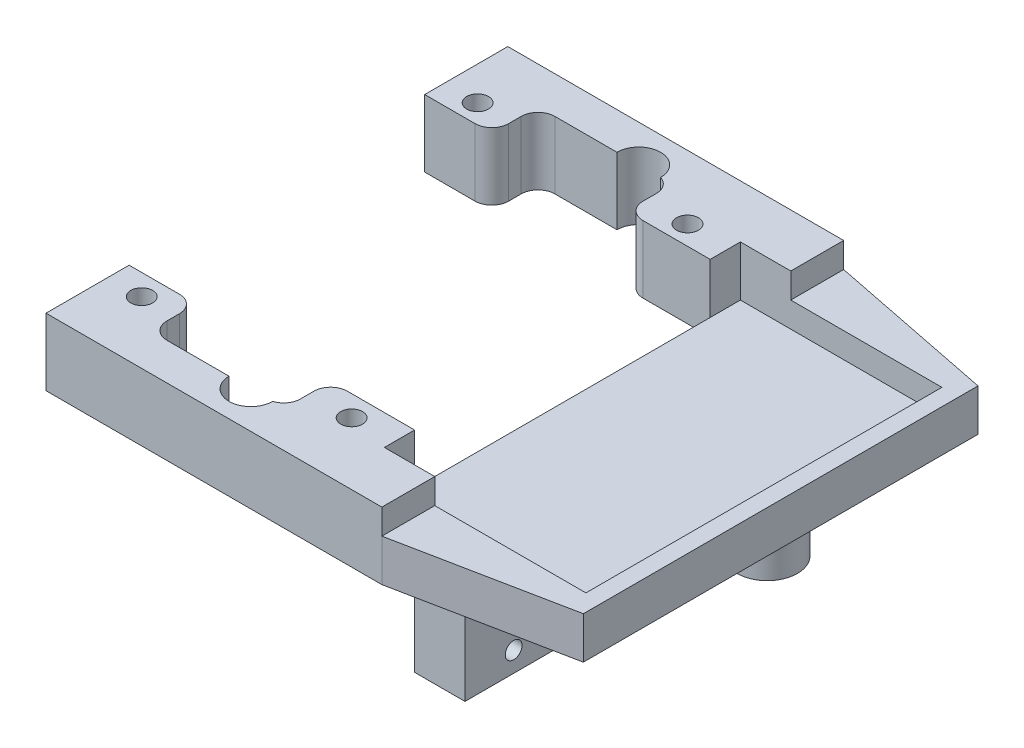
SolidWorks part; units mm, degrees
ref_plane "Front Plane" through (0, 0, 0) normal (0, 0, 1) x (1, 0, 0)
ref_plane "Top Plane" through (0, 0, 0) normal (0, 1, 0) x (1, 0, 0)
ref_plane "Right Plane" through (0, 0, 0) normal (1, 0, 0) x (0, 0, -1)
sketch "Sketch1" plane through (0, 0, 0) normal (0, 1, 0) x (1, 0, 0)
  line L0 (50.8, -0.508) -> (25.4, -5.588)
  line L1 (0, 0) -> (25.4, 0) construction
  line L2 (0, 0) -> (0, 58.674) construction
  line L3 (0, 58.674) -> (25.4, 58.674) construction
  line L4 (25.4, 0) -> (25.4, 58.674) construction
  line L5 (-25.4, 64.262) -> (25.4, 64.262)
  line L6 (-25.4, 64.262) -> (-25.4, -5.588)
  line L7 (-25.4, -5.588) -> (25.4, -5.588)
  line L8 (25.4, 64.262) -> (25.4, -5.588)
  line L9 (25.4, 59.182) -> (50.8, 59.182)
  line L10 (25.4, 59.182) -> (25.4, -0.508)
  line L11 (25.4, -0.508) -> (50.8, -0.508)
  line L12 (50.8, 59.182) -> (50.8, -0.508)
  line L13 (50.8, 59.182) -> (25.4, 64.262)
  circle A0 centre (0, 0) radius 3.302
  circle A1 centre (0, 58.674) radius 3.302
  circle A2 centre (11.43, 54.61) radius 1.651
  circle A3 centre (-20.32, 54.61) radius 1.651
  circle A4 centre (11.43, 3.81) radius 1.651
  circle A5 centre (-20.32, 54.61) radius 1.651
  circle A6 centre (-20.32, 3.81) radius 1.651
  circle A7 centre (11.43, 3.81) radius 1.651
  dimension "D1" = 6.604
  dimension "D3" = 6.604
  dimension "D11" = 11.43
  dimension "D12" = 4.064
  dimension "D17" = 3.302
  dimension "D2" = 58.674
  dimension "D4" = 25.4
  dimension "D5" = 69.85
  dimension "D6" = 5.588
  dimension "D7" = 50.8
  dimension "D8" = 25.4
  dimension "D9" = 59.69
  dimension "D10" = 5.08
  dimension "D13" = 2
  dimension "D14" = 2
  dimension "D15" = 2
  dimension "D16" = 2
extrude "Boss-Extrude1" add sketch "Sketch1" along normal blind 6.35 contours L8 L5 L6 L7 A1 A0 | L9 L13 L8 | L12 L9 L8 L11 | L11 L8 L0 region at (33.8667, 0, 2.2013) region at (38.1, 0, -29.337) region at (0.0442, 0, -29.3383) region at (33.8667, 0, -60.8753)
sketch "Sketch2" plane through (0, 6.35, 0) normal (0, 1, 0) x (1, 0, 0)
  line L0 (50.8, 59.182) -> (50.8, -0.508) construction
  line L5 (25.4, 64.262) -> (25.4, -5.588) construction
  line L6 (50.8, 59.182) -> (-25.4, 59.182) construction
  line L7 (-25.4, 64.262) -> (-25.4, -5.588) construction
  line L8 (50.8, -0.508) -> (-25.4, -0.508) construction
  line L9 (17.78, 56.261) -> (48.26, 56.261)
  line L14 (17.78, 56.261) -> (17.78, 2.413)
  line L15 (17.78, 2.413) -> (48.26, 2.413)
  line L16 (48.26, 56.261) -> (48.26, 2.413)
  dimension "D1" = 30.48
  dimension "D2" = 53.848
  dimension "D3" = 2.921
  dimension "D4" = 2.54
  dimension "D5" = 2.921
extrude "Cut-Extrude1" cut sketch "Sketch2" against normal blind 3.81
sketch "Sketch3" plane through (0, 6.35, 0) normal (0, 1, 0) x (1, 0, 0)
  line L0 (-25.4, 64.262) -> (-25.4, -5.588) construction
  line L1 (-25.4, 51.689) -> (17.78, 51.689)
  line L2 (-25.4, 51.689) -> (-25.4, 6.985)
  line L3 (-25.4, 6.985) -> (17.78, 6.985)
  line L4 (17.78, 51.689) -> (17.78, 6.985)
  line L5 (25.4, 64.262) -> (25.4, -5.588) construction
  line L7 (-25.4, 64.262) -> (25.4, 64.262) construction
  line L8 (-15.24, 51.689) -> (5.08, 51.689)
  line L9 (-15.24, 51.689) -> (-15.24, 58.674)
  line L10 (-15.24, 58.674) -> (5.08, 58.674)
  line L11 (5.08, 51.689) -> (5.08, 58.674)
  line L12 (-15.24, 6.985) -> (5.08, 6.985)
  line L13 (-15.24, 6.985) -> (-15.24, 0)
  line L14 (-15.24, 0) -> (5.08, 0)
  line L15 (5.08, 6.985) -> (5.08, 0)
  line M5 (17.78, 2.413) -> (17.78, 56.261)
  line M13 (-25.4, 64.262) -> (-25.4, -5.588)
  circle M15 centre (0, 58.674) radius 3.302
  circle M16 centre (0, 0) radius 3.302
  dimension "D1" = 44.704
  dimension "D2" = 12.573
  dimension "D3" = 10.16
  dimension "D4" = 20.32
  dimension "D5" = 58.674
  dimension "D6" = 6.985
  dimension "D7" = 6.985
  dimension "D8" = 7.62
extrude "Cut-Extrude2" cut sketch "Sketch3" against normal through all contours L1 L11 L10 L9 M15 | L3 L1 M13 M5 | L15 L3 L13 L14 M16 region at (-3.81, 6.35, -29.337) region at (-5.7771, 6.35, -54.8946) region at (-5.7771, 6.35, -3.7794)
sketch "Sketch13" plane through (0, 6.35, 0) normal (0, 1, 0) x (1, 0, 0)
  line L1 (-25.4, 51.689) -> (25.4, 51.689)
  line L2 (-25.4, 51.689) -> (-25.4, 64.262)
  line L3 (-25.4, 64.262) -> (25.4, 64.262)
  line L4 (25.4, 51.689) -> (25.4, 64.262)
  line L5 (-25.4, 6.985) -> (25.4, 6.985)
  line L6 (-25.4, 6.985) -> (-25.4, -5.588)
  line L7 (-25.4, -5.588) -> (25.4, -5.588)
  line L8 (25.4, 6.985) -> (25.4, -5.588)
  line L9 (17.78, 56.261) -> (25.4, 56.261)
  line L10 (17.78, 56.261) -> (17.78, 51.689)
  line L11 (17.78, 51.689) -> (25.4, 51.689)
  line L12 (25.4, 56.261) -> (25.4, 51.689)
  line L13 (17.78, 2.413) -> (25.4, 2.413)
  line L14 (17.78, 2.413) -> (17.78, 6.985)
  line L15 (17.78, 6.985) -> (25.4, 6.985)
  line L16 (25.4, 2.413) -> (25.4, 6.985)
  circle M1 centre (-20.32, 3.81) radius 1.651
  circle M2 centre (11.43, 3.81) radius 1.651
  circle M3 centre (-20.32, 54.61) radius 1.651
  circle M4 centre (11.43, 54.61) radius 1.651
  arc M5 (-3.302, 58.674) -> (3.302, 58.674) centre (0, 58.674) cw
  line M6 (3.302, 58.674) -> (5.08, 58.674)
  line M7 (5.08, 58.674) -> (5.08, 51.689)
  line M8 (5.08, 51.689) -> (17.78, 51.689)
  line M9 (17.78, 51.689) -> (17.78, 56.261)
  line M10 (17.78, 56.261) -> (48.26, 56.261)
  line M12 (48.26, 2.413) -> (17.78, 2.413)
  line M13 (17.78, 2.413) -> (17.78, 6.985)
  line M14 (17.78, 6.985) -> (5.08, 6.985)
  line M15 (5.08, 6.985) -> (5.08, 0)
  line M16 (5.08, 0) -> (3.302, 0)
  arc M17 (3.302, 0) -> (-3.302, 0) centre (0, 0) cw
  line M18 (-3.302, 0) -> (-15.24, 0)
  line M19 (-15.24, 0) -> (-15.24, 6.985)
  line M20 (-15.24, 6.985) -> (-25.4, 6.985)
  line M21 (-25.4, 6.985) -> (-25.4, -5.588)
  line M22 (-25.4, -5.588) -> (25.4, -5.588)
  line M26 (25.4, 64.262) -> (-25.4, 64.262)
  line M27 (-25.4, 64.262) -> (-25.4, 51.689)
  line M28 (-25.4, 51.689) -> (-15.24, 51.689)
  line M29 (-15.24, 51.689) -> (-15.24, 58.674)
  line M30 (-15.24, 58.674) -> (-3.302, 58.674)
extrude "Boss-Extrude7" add sketch "Sketch13" along normal blind 3.81 contours L4 M10 M26 M27 M28 M29 M30 M5 M6 M7 M8 M9 M3 M4 | L8 M12 M13 M14 M15 M16 M17 M18 M19 M20 M21 M22 M2 M1 region at (-24.8767, 6.35, -57.9755) region at (-20.32, 6.35, -6.4617)
sketch "Sketch15" plane through (0, 0, 0) normal (0, -1, 0) x (1, 0, 0)
  line L0 (25.4, 5.588) -> (25.4, -64.262) construction
  line L1 (5.08, -6.985) -> (17.78, -6.985) construction
  line L2 (17.78, -6.985) -> (25.4, -6.985)
  line L3 (17.78, -6.985) -> (17.78, -51.689)
  line L4 (17.78, -51.689) -> (25.4, -51.689)
  line L5 (25.4, -6.985) -> (25.4, -51.689)
  line L6 (5.08, -51.689) -> (17.78, -51.689) construction
  dimension "D1" = 44.704
extrude "Boss-Extrude8" add sketch "Sketch15" along normal blind 21.59
sketch "Sketch16" plane through (17.78, 0, 0) normal (-1, 0, 0) x (0, 0, 1)
  line L0 (-6.985, -21.59) -> (-51.689, -21.59) construction
  line L1 (-51.689, -21.59) -> (-51.689, 0) construction
  circle A0 centre (-44.323, -18.542) radius 1.27
  circle A1 centre (-34.671, -18.542) radius 1.27
  circle A2 centre (-24.003, -18.542) radius 1.27
  circle A3 centre (-14.351, -18.542) radius 1.27
  dimension "D1" = 2.54
  dimension "D2" = 3.048
  dimension "D7" = 7.366
  dimension "D3" = 2
  dimension "D4" = 2
  dimension "D5" = 2
extrude "Cut-Extrude3" cut sketch "Sketch16" against normal through all
fillet "Fillet1" radius 2.54 8 edges at (-15.24, 5.08, -6.985) (-15.24, 5.08, 0) (5.08, 5.08, 0) (5.08, 5.08, -6.985) (5.08, 5.08, -51.689) (-15.24, 5.08, -51.689) (-15.24, 5.08, -58.674) (5.08, 5.08, -58.674)
sketch "Sketch17" plane through (0, 0, 0) normal (0, -1, 0) x (1, 0, 0)
  line L0 (25.4, -51.689) -> (25.4, -6.985) construction
  line L1 (25.4, -6.985) -> (17.78, -6.985) construction
  line L2 (25.4, -51.689) -> (25.4, -6.985) construction
  line L3 (29.21, -14.224) -> (25.4, -14.224)
  line L4 (29.21, -14.224) -> (29.21, -7.366)
  line L5 (29.21, -7.366) -> (25.4, -7.366)
  line L6 (25.4, -14.224) -> (25.4, -7.366)
  circle A0 centre (29.21, -10.795) radius 3.429
  circle A1 centre (41.91, -36.195) radius 4.572
  dimension "D1" = 9.144
  dimension "D2" = 6.858
  dimension "D3" = 12.7
  dimension "D4" = 25.4
  dimension "D6" = 3.81
  dimension "D5" = 3.81
extrude "Boss-Extrude9" add sketch "Sketch17" along normal blind 8.89 contours L4 A0 | A1 | L3 L6 L5 L4 region at (30.6653, 0, -10.795) region at (41.91, 0, -36.195)
sketch "Sketch18" plane through (0, -8.89, 0) normal (0, -1, 0) x (1, 0, 0)
  line L0 (29.21, -7.366) -> (29.21, -14.224) construction
  circle A0 centre (29.21, -10.795) radius 2.032
  circle A2 centre (41.91, -36.195) radius 2.032
  dimension "D1" = 4.064
  dimension "D2" = 4.064
extrude "Cut-Extrude4" cut sketch "Sketch18" against normal blind 5.08
fillet "Fillet2" radius 2.54 2 edges at (25.4, 0, -32.9565) (41.91, 0, -31.623)
